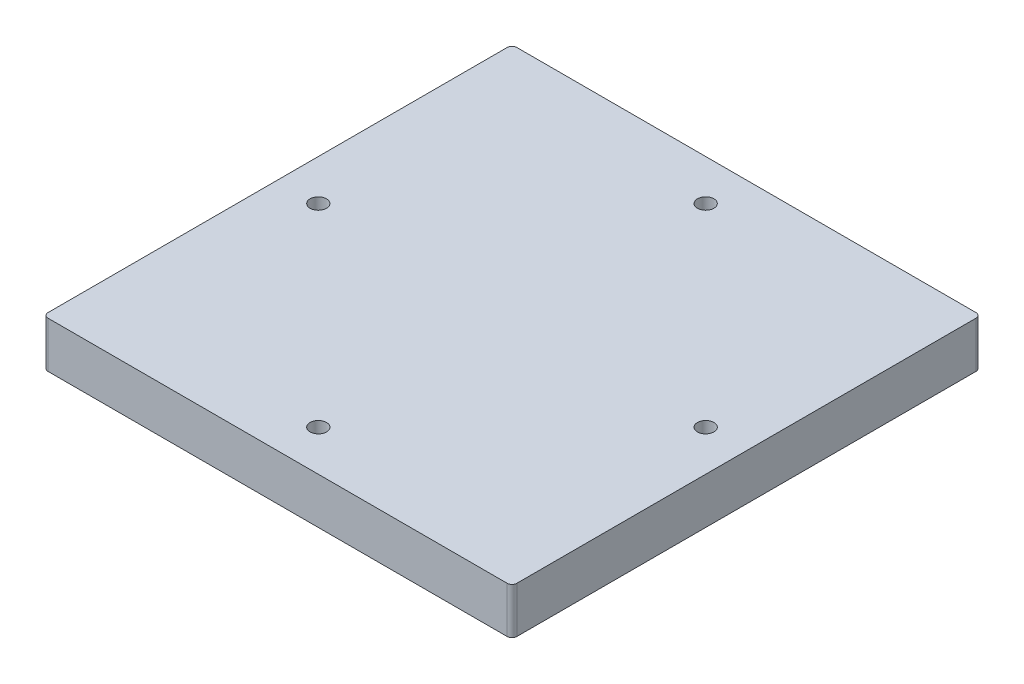
SolidWorks part; units mm, degrees
material "6061-T6 (SS)"
ref_plane "Front Plane" through (0, 0, 0) normal (0, 0, 1) x (1, 0, 0)
ref_plane "Top Plane" through (0, 0, 0) normal (0, 1, 0) x (1, 0, 0)
ref_plane "Right Plane" through (0, 0, 0) normal (1, 0, 0) x (0, 0, -1)
sketch "Sketch1" plane through (0, 0, 0) normal (0, 1, 0) x (1, 0, 0)
  line L1 (48.4125, -48.4125) -> (-48.4125, -48.4125)
  line L2 (48.4125, -48.4125) -> (48.4125, 48.4125)
  line L3 (48.4125, 48.4125) -> (-48.4125, 48.4125)
  line L4 (-48.4125, -48.4125) -> (-48.4125, 48.4125)
  line L5 (48.4125, -48.4125) -> (-48.4125, 48.4125) construction
  line L6 (48.4125, 48.4125) -> (-48.4125, -48.4125) construction
  point P0 (0, 0)
  dimension "D1" = 96.825
extrude "Boss-Extrude1" add sketch "Sketch1" along normal mid plane 9.525
fillet "Fillet1" radius 1 4 edges at (-48.4125, 0, -48.4125) (48.4125, 0, -48.4125) (48.4125, 0, 48.4125) (-48.4125, 0, 48.4125)
sketch "Sketch4" plane through (0, 4.7625, 0) normal (0, 1, 0) x (1, 0, 0)
  point P0 (-40, 0)
  point P2 (0, 40)
  point P4 (40, 0)
  point P6 (0, -40)
  point P9 (-2.3329, -41.8622)
  point P10 (41.3438, 0)
  point P11 (0, 41.0846)
  point P12 (-39.1405, 0)
  point P13 (0, 0)
  dimension "D1" = 40
  dimension "D2" = 40
  dimension "D3" = 40
  dimension "D4" = 40
hole_wizard "M3 Clearance Hole1" positions "Sketch4" profile "Sketch3" hole size "M3" standard "ANSI Metric" end condition through all
sketch "Sketch3" plane through (-40, 4.7625, 0) normal (1, 0, 0) x (0, 0, 1)
  line L0 (0, 0) -> (0, 9.525)
  line L1 (0, 9.525) -> (1.7, 9.525)
  line L2 (1.7, 9.525) -> (1.7, 0)
  line L5 (1.7, 0) -> (0, 0)
  line L11 (0, -6.35) -> (0, 107.95) construction
  dimension "Thru Hole Dia." = 3.4
  dimension "Thru Hole Depth" = 9.525
